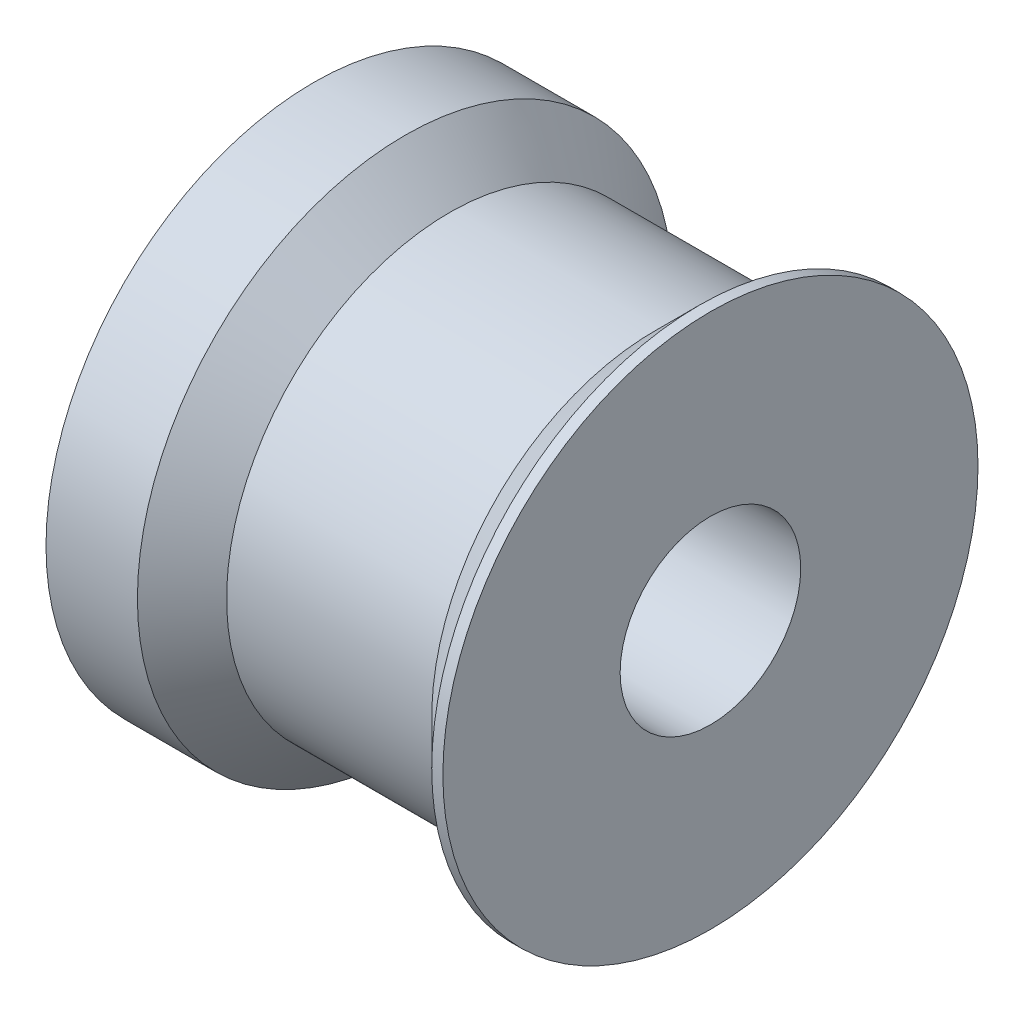
SolidWorks part; units mm, degrees
ref_plane "Front Plane" through (0, 0, 0) normal (0, 0, 1) x (1, 0, 0)
ref_plane "Top Plane" through (0, 0, 0) normal (0, 1, 0) x (1, 0, 0)
ref_plane "Right Plane" through (0, 0, 0) normal (1, 0, 0) x (0, 0, -1)
sketch "Sketch2" plane through (0, 0, 0) normal (0, 1, 0) x (1, 0, 0)
  line L0 (-7.1, 12) -> (-6.6, 12)
  line L1 (-6.6, 12) -> (-4.6, 10)
  line L2 (-4.6, 10) -> (4.6, 10)
  line L3 (4.6, 10) -> (6.6, 12)
  line L4 (6.6, 12) -> (7.1, 12)
  line L5 (7.1, 12) -> (7.1, 0)
  line L6 (-7.1, 12) -> (-7.1, 0) construction
  line L7 (-54.6936, 0) -> (47.2254, 0) construction
  line L8 (0, -23.2469) -> (0, 34.557) construction
  line L9 (7.1, 0) -> (-7.1, 0)
  line L10 (-7.1, 12) -> (-7.7, 12)
  line L11 (-7.7, 12) -> (-7.7, 0)
  line L12 (-7.7, 0) -> (-7.1, 0)
  line L13 (-7.1, 0) -> (-7.7, 0)
  point P16 (0, 10)
  dimension "D1" = 12
  dimension "D2" = 2.5
  dimension "D3" = 9.2
  dimension "D4" = 10
  dimension "D5" = 0.6
revolve "Revolve1" add sketch "Sketch2" angle 360 about L9 region at (-0.3433, 0, -5.2698)
sketch "Sketch3" plane through (-7.7, 0, 0) normal (-1, 0, 0) x (0, 0, 1)
  circle A0 centre (0, 0) radius 2
  dimension "D1" = 4
extrude "Cut-Extrude1" cut sketch "Sketch3" against normal up to surface (14.8 mm away) up to face at (7.1, 0, -12)
sketch "Sketch4" plane through (-7.7, 0, 0) normal (-1, 0, 0) x (0, 0, 1)
  circle A0 centre (0, 0) radius 4.05
  dimension "D1" = 8.1
extrude "Cut-Extrude2" cut sketch "Sketch4" against normal up to surface (14.8 mm away) from offset 2 up to face at (7.1, 0, 2) offset against normal yes
sketch "Sketch5" plane through (-7.7, 0, 0) normal (-1, 0, 0) x (0, 0, 1)
  circle A3 centre (0, 0) radius 12
  circle A4 centre (0, 0) radius 12
  circle A6 centre (0, 0) radius 2
  circle A7 centre (0, 0) radius 2
  dimension "D1" = 0
  dimension "D2" = 0
extrude "Boss-Extrude1" add sketch "Sketch5" along normal blind 3
